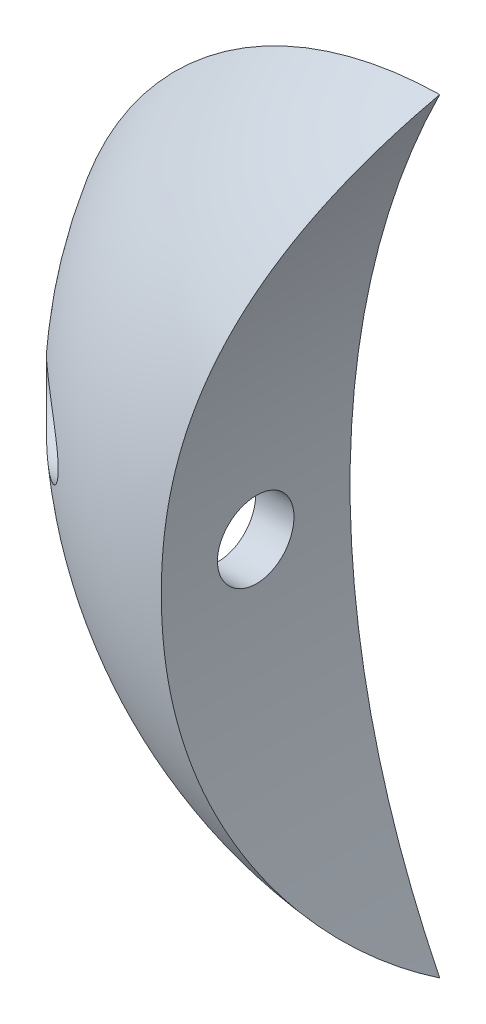
SolidWorks part; units mm, degrees
ref_plane "前视基准面" through (0, 0, 0) normal (0, 0, 1) x (1, 0, 0)
ref_plane "上视基准面" through (0, 0, 0) normal (0, 1, 0) x (1, 0, 0)
ref_plane "右视基准面" through (0, 0, 0) normal (1, 0, 0) x (0, 0, -1)
other "Configuration Table"
sketch "Sketch1" plane through (0, 0, 0) normal (0, 0, 1) x (1, 0, 0)
  line L0 (0, 0) -> (20, 0) construction
  line L1 (0, 0) -> (12.2305, 0) construction
  line L2 (-0.1563, 9.9988) -> (-0.1563, -9.9988) construction
  arc A0 (-0.1563, 9.9988) -> (-0.1563, -9.9988) centre (0, 0) ccw
  arc A1 (-0.1563, 9.9988) -> (-0.1563, -9.9988) centre (20, 0) ccw
  dimension "D1" = 20
  dimension "D4" = 45
  dimension "D2" = 0
  dimension "D3" = 20
extrude "Boss-Extrude1" add sketch "Sketch1" along normal blind 5
fillet "Fillet1" radius 10 1 edges at (-10, 0, 5)
shell "Shell1" thickness 1 removed face at (-6.25, 0, 0)
sketch "Sketch4" plane through (0, 0, 0) normal (1, 0, 0) x (0, 0, -1)
  line L0 (0, 0) -> (-4.9325, 0) construction
  line L1 (0, -9.9988) -> (0, 9.9988) construction
  line L2 (-4.9325, 0) -> (-2.4662, 0) construction
  circle A0 centre (-2.4662, 0) radius 1
  spline S0 degree 3 poles (0, 9.9988) (-0.846, 9.5065) (-1.5866, 8.9036) (-2.3941, 8.0113) (-2.5501, 7.8251) (-2.8455, 7.4437) (-2.9854, 7.2482) (-3.3828, 6.647) (-3.6179, 6.227) (-4.0306, 5.3482) (-4.2087, 4.8862) (-4.4998, 3.9487) (-4.614, 3.4709) (-4.787, 2.4985) (-4.8455, 2.0027) (-4.9179, 1.0012) (-4.9325, 0.4994) (-4.9324, -0.5029) (-4.9177, -1.0039) (-4.8452, -2.0055) (-4.7869, -2.4989) (-4.6144, -3.4688) (-4.5006, -3.9453) (-4.2107, -4.8804) (-4.0328, -5.3429) (-3.4133, -6.6638) (-2.8893, -7.4617) (-2.082, -8.3569) (-1.9124, -8.5309) (-1.5625, -8.8631) (-1.3816, -9.022) (-0.821, -9.4773) (-0.4233, -9.7524) (0, -9.9988) knots 0 0 0 0 0.125 0.125 0.15625 0.15625 0.1875 0.1875 0.25 0.25 0.3125 0.3125 0.375 0.375 0.4375 0.4375 0.5 0.5 0.5625 0.5625 0.625 0.625 0.6875 0.6875 0.75 0.75 0.875 0.875 0.90625 0.90625 0.9375 0.9375 1 1 1 1 construction
  dimension "D1" = 2
extrude "Cut-Extrude1" cut sketch "Sketch4" against normal through all
